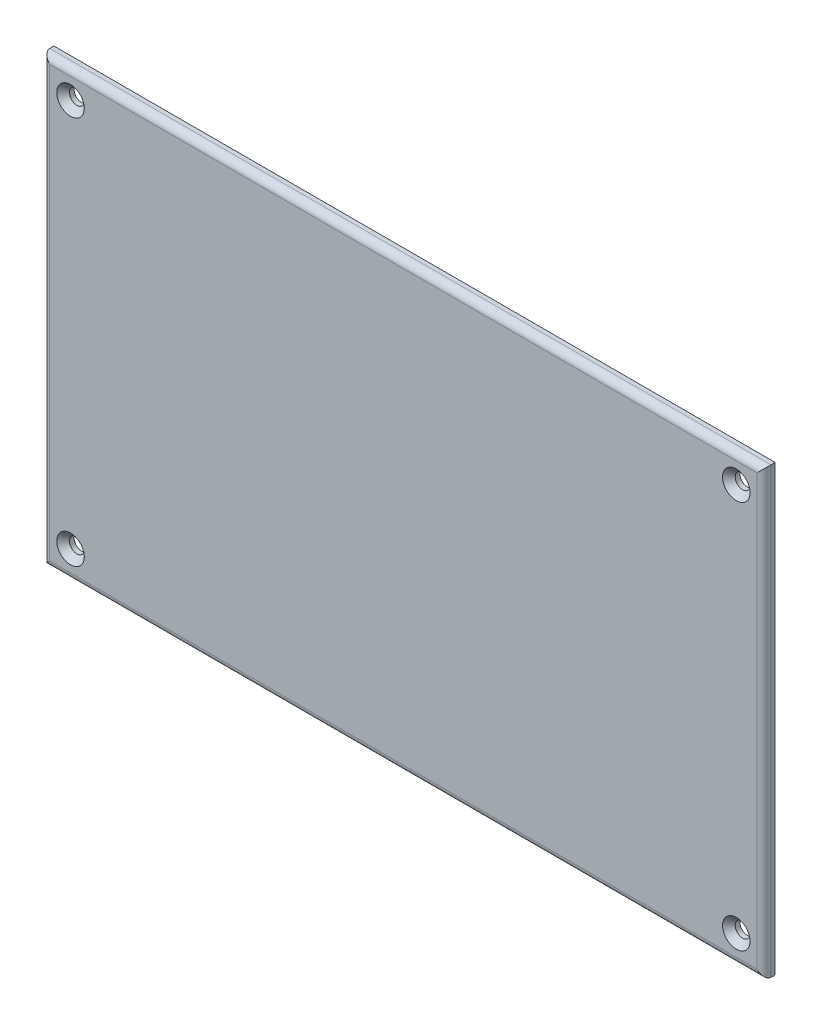
SolidWorks part; units mm, degrees
material "PET"
ref_plane "Front Plane" through (0, 0, 0) normal (0, 0, 1) x (1, 0, 0)
ref_plane "Top Plane" through (0, 0, 0) normal (0, 1, 0) x (1, 0, 0)
ref_plane "Right Plane" through (0, 0, 0) normal (1, 0, 0) x (0, 0, -1)
sketch "Sketch1" plane through (0, 0, 0) normal (0, 0, 1) x (1, 0, 0)
  line L1 (0, 0) -> (165.1, 0)
  line L2 (0, 0) -> (0, 101.6)
  line L3 (0, 101.6) -> (165.1, 101.6)
  line L4 (165.1, 0) -> (165.1, 101.6)
  dimension "D1" = 165.1
  dimension "D2" = 101.6
extrude "Boss-Extrude1" add sketch "Sketch1" along normal blind 2.54
fillet "Fillet1" radius 1.5875 4 edges at (82.55, 101.6, 2.54) (165.1, 50.8, 2.54) (82.55, 0, 2.54) (0, 50.8, 2.54)
hole_wizard "CSK for M3 Flat Head Machine Screw1" positions "Sketch3" profile "Sketch4" countersink size "M3" standard "ANSI Metric"
sketch "Sketch3" plane through (0, 0, 2.54) normal (0, 0, 1) x (1, 0, 0)
  line L0 (6.35, 6.35) -> (6.35, 95.25) construction
  line L1 (6.35, 95.25) -> (158.75, 95.25) construction
  line L3 (82.55, 95.25) -> (82.55, 101.6) construction
  line L4 (0, 101.6) -> (165.1, 101.6) construction
  line L6 (6.35, 50.8) -> (0, 50.8) construction
  line L7 (0, 0) -> (0, 101.6) construction
  point P0 (6.35, 95.25)
  point P2 (6.35, 6.35)
  point P4 (158.75, 6.35)
  point P6 (158.75, 95.25)
  dimension "D1" = 152.4
  dimension "D2" = 88.9
sketch "Sketch4" plane through (6.35, 95.25, 2.54) normal (1, 0, 0) x (0, -1, 0)
  line L0 (0, 0) -> (0, 7.3715)
  line L1 (0, 7.3715) -> (1.7, 6.35)
  line L2 (1.7, 6.35) -> (1.7, 1.45)
  line L3 (1.7, 1.45) -> (3.15, 0)
  line L5 (3.15, 0) -> (0, 0)
  line L6 (-1.7, 1.45) -> (-3.15, 0) construction
  line L10 (0, 7.3715) -> (-1.7, 6.35) construction
  line L11 (0, -6.35) -> (0, 107.95) construction
  dimension "Hole Dia." = 3.4
  dimension "Hole Depth" = 6.35
  dimension "Near C'Sink Dia." = 6.3
  dimension "Near C'Sink Angle" = 90
  dimension "Drill Angle" = 118
